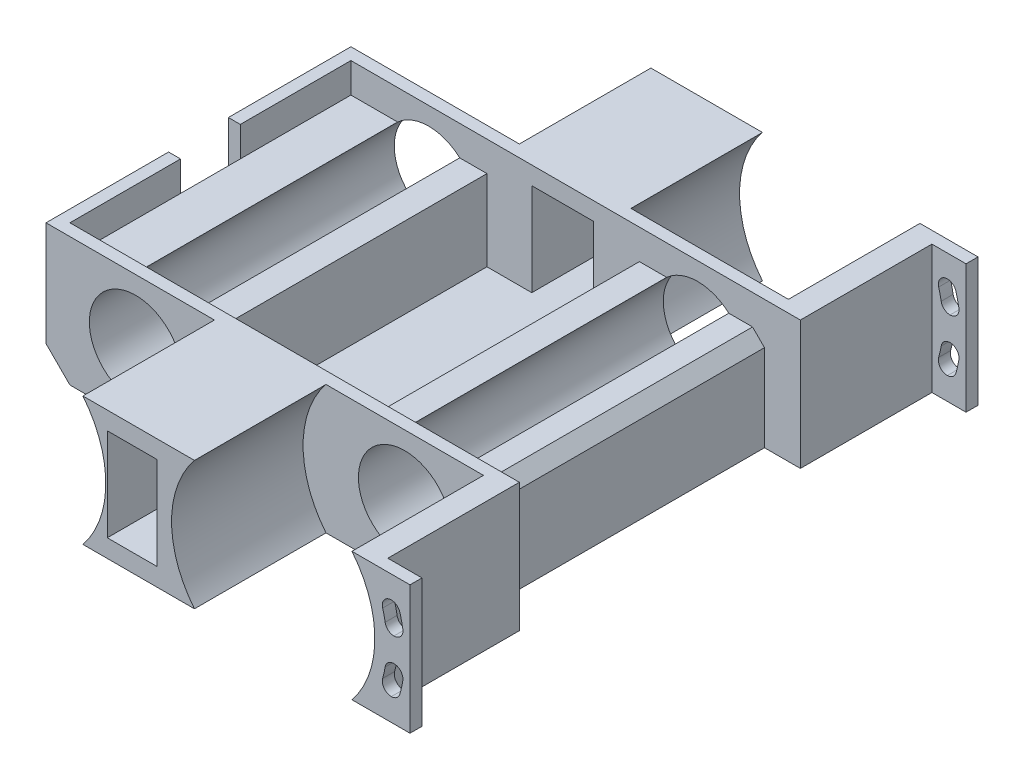
SolidWorks part; units mm, degrees
ref_plane "Front Plane" through (0, 0, 0) normal (0, 0, 1) x (1, 0, 0)
ref_plane "Top Plane" through (0, 0, 0) normal (0, 1, 0) x (1, 0, 0)
ref_plane "Right Plane" through (0, 0, 0) normal (1, 0, 0) x (0, 0, -1)
sketch "Sketch1" plane through (0, 0, 0) normal (0, 1, 0) x (1, 0, 0)
  line L1 (-44.2281, 29.9937) -> (50.7719, 29.9937)
  line L2 (-44.2281, 29.9937) -> (-44.2281, -65.0063)
  line L3 (-44.2281, -65.0063) -> (50.7719, -65.0063)
  line L4 (50.7719, 29.9937) -> (50.7719, -65.0063)
  dimension "D1" = 95
  dimension "D2" = 95
extrude "Boss-Extrude1" add sketch "Sketch1" along normal blind 25
sketch "Sketch2" plane through (0, 0, 65.0063) normal (0, 0, 1) x (1, 0, 0)
  line L1 (-44.2281, 0) -> (50.7719, 0) construction
  line L2 (-44.2281, 25) -> (-44.2281, 0) construction
  circle A0 centre (-29.2281, 10.75) radius 7.75
  circle A1 centre (15.7719, 10.75) radius 7.75
  point P6 (-44.2281, 12.5)
  dimension "D1" = 45
  dimension "D2" = 10.75
  dimension "D3" = 15
extrude "Cut-Extrude2" cut sketch "Sketch2" against normal blind 100
sketch "Sketch3" plane through (0, 0, 65.0063) normal (0, 0, 1) x (1, 0, 0)
  line L0 (-44.2281, 0) -> (50.7719, 0) construction
  circle A0 centre (-29.2281, 10.75) radius 17
  circle A1 centre (15.7719, 10.75) radius 17
  point P7 (-28.0903, 8.1892)
  dimension "D1" = 45
  dimension "D2" = 10.75
extrude "Cut-Extrude3" cut sketch "Sketch3" against normal blind 22
sketch "Sketch4" plane through (0, 0, -29.9937) normal (0, 0, -1) x (-1, 0, 0)
  circle A0 centre (-15.7719, 10.75) radius 17
  circle A1 centre (29.2281, 10.75) radius 17
extrude "Cut-Extrude4" cut sketch "Sketch4" against normal blind 22
sketch "Sketch5" plane through (0, 0, 65.0063) normal (0, 0, 1) x (1, 0, 0)
  line L1 (-44.2281, 25) -> (-37.9811, 25)
  line L2 (-44.2281, 25) -> (-44.2281, 0)
  line L3 (-44.2281, 0) -> (-37.9811, 0)
  line L4 (-37.9811, 25) -> (-37.9811, 0)
extrude "Cut-Extrude5" cut sketch "Sketch5" against normal blind 22
sketch "Sketch6" plane through (0, 0, -29.9937) normal (0, 0, -1) x (-1, 0, 0)
  line L1 (44.2281, 25) -> (37.0493, 25)
  line L2 (44.2281, 25) -> (44.2281, 0)
  line L3 (44.2281, 0) -> (37.0493, 0)
  line L4 (37.0493, 25) -> (37.0493, 0)
extrude "Cut-Extrude6" cut sketch "Sketch6" against normal blind 22
sketch "Sketch8" plane through (0, 0, -29.9937) normal (0, 0, -1) x (-1, 0, 0)
  line L1 (-50.7719, 25) -> (48.732, 25)
  line L2 (-50.7719, 25) -> (-50.7719, 21.5)
  line L3 (-50.7719, 21.5) -> (48.732, 21.5)
  line L4 (48.732, 25) -> (48.732, 21.5)
  dimension "D1" = 3.5
extrude "Cut-Extrude7" cut sketch "Sketch8" against normal blind 100
sketch "Sketch9" plane through (0, 0, 65.0063) normal (0, 0, 1) x (1, 0, 0)
  line L0 (-16.0585, 0) -> (2.6024, 0) construction
  line L1 (-11.9781, 18.5) -> (-3.6781, 18.5)
  line L2 (-11.9781, 18.5) -> (-11.9781, 3)
  line L3 (-11.9781, 3) -> (-3.6781, 3)
  line L4 (-3.6781, 18.5) -> (-3.6781, 3)
  arc A0 (-16.0585, 0) -> (-16.0585, 21.5) centre (-29.2281, 10.75) ccw construction
  circle A1 centre (15.7719, 10.75) radius 7.75 construction
  dimension "D1" = 8.3
  dimension "D2" = 15.5
  dimension "D3" = 3
  dimension "D4" = 17.25
  dimension "D5" = 19.45
extrude "Cut-Extrude11" cut sketch "Sketch9" against normal blind 100
sketch "Sketch13" plane through (-3.6781, 0, 0) normal (-1, 0, 0) x (0, 0, 1)
  line L0 (-29.9937, 3) -> (65.0063, 3) construction
  line L1 (-25.9937, 3) -> (61.0063, 3)
  line L2 (-25.9937, 3) -> (-25.9937, 18.5)
  line L3 (-25.9937, 18.5) -> (61.0063, 18.5)
  line L4 (61.0063, 3) -> (61.0063, 18.5)
  line L5 (-29.9937, 18.5) -> (65.0063, 18.5) construction
  line L6 (-29.9937, 3) -> (-29.9937, 18.5) construction
  line L7 (65.0063, 3) -> (65.0063, 18.5) construction
  dimension "D1" = 4
  dimension "D2" = 4
extrude "Cut-Extrude12" cut sketch "Sketch13" against normal blind 2
sketch "Sketch14" plane through (0, 21.5, 0) normal (0, 1, 0) x (1, 0, 0)
  line L2 (6.0219, 5.9937) -> (6.0219, -41.0063)
  line L4 (-19.4781, 5.9937) -> (-19.4781, -41.0063)
  line L7 (6.0219, 5.9937) -> (-19.4781, 5.9937)
  line L9 (6.0219, -41.0063) -> (-19.4781, -41.0063)
  dimension "D2" = 2
extrude "Cut-Extrude14" cut sketch "Sketch14" against normal blind 18.5
sketch "Sketch16" plane through (0, 21.5, 0) normal (0, 1, 0) x (1, 0, 0)
  line L0 (-44.2281, -43.0063) -> (-44.2281, 7.9937) construction
  line L1 (-17.4781, 5.9937) -> (-42.2281, 5.9937)
  line L2 (-17.4781, 5.9937) -> (-17.4781, -41.0063)
  line L3 (-17.4781, -41.0063) -> (-42.2281, -41.0063)
  line L4 (-42.2281, 5.9937) -> (-42.2281, -41.0063)
  line L5 (-44.2281, -43.0063) -> (-16.0585, -43.0063) construction
  line L6 (-16.0585, 7.9937) -> (-44.2281, 7.9937) construction
  dimension "D1" = 2
  dimension "D2" = 2
  dimension "D3" = 2
  dimension "D4" = 2
extrude "Cut-Extrude15" cut sketch "Sketch16" against normal blind 5
sketch "Sketch17" plane through (0, 21.5, 0) normal (0, 1, 0) x (1, 0, 0)
  line L0 (2.6024, -43.0063) -> (28.9415, -43.0063) construction
  line L1 (6.0219, 5.9937) -> (26.9415, 5.9937)
  line L2 (6.0219, 5.9937) -> (6.0219, -41.0063)
  line L3 (6.0219, -41.0063) -> (26.9415, -41.0063)
  line L4 (26.9415, 5.9937) -> (26.9415, -41.0063)
  dimension "D1" = 2
  dimension "D2" = 2
extrude "Cut-Extrude16" cut sketch "Sketch17" against normal blind 5
sketch "Sketch18" plane through (0, 0, 65.0063) normal (0, 0, 1) x (1, 0, 0)
  line L0 (34.6664, 12.75) -> (37.6809, 12.75)
  line L2 (34.6664, 8.75) -> (37.6809, 8.75)
  line L3 (33.4355, 17.75) -> (36.6286, 17.75)
  line L4 (33.4355, 3.75) -> (36.6286, 3.75)
  arc A0 (36.6286, 3.75) -> (37.6809, 8.75) centre (15.7719, 10.75) ccw
  arc A1 (33.4355, 3.75) -> (34.6664, 8.75) centre (15.7719, 10.75) ccw
  arc A2 (34.6664, 12.75) -> (33.4355, 17.75) centre (15.7719, 10.75) ccw
  arc A3 (37.6809, 12.75) -> (36.6286, 17.75) centre (15.7719, 10.75) ccw
  dimension "D1" = 44
  dimension "D2" = 38
  dimension "D4" = 5
  dimension "D6" = 5
extrude "Cut-Extrude17" cut sketch "Sketch18" against normal blind 100
fillet "Fillet6" radius 1.5 2 edges at (33.4355, 17.75, 17.5063) (36.6286, 17.75, 17.5063)
fillet "Fillet7" radius 1.5 2 edges at (37.6809, 12.75, 17.5063) (34.6664, 12.75, 17.5063)
fillet "Fillet8" radius 1.5 2 edges at (33.4355, 3.75, 17.5063) (36.6286, 3.75, 17.5063)
fillet "Fillet9" radius 1.5 2 edges at (37.6809, 8.75, 17.5063) (34.6664, 8.75, 17.5063)
sketch "Sketch19" plane through (0, 0, 65.0063) normal (0, 0, 1) x (1, 0, 0)
  line L1 (28.9415, 0) -> (50.7719, 0) construction
  line L2 (38.6507, 0) -> (50.7719, 0)
  line L3 (38.6507, 0) -> (38.6507, 21.5)
  line L4 (38.6507, 21.5) -> (50.7719, 21.5)
  line L5 (50.7719, 0) -> (50.7719, 21.5)
extrude "Cut-Extrude20" cut sketch "Sketch19" against normal blind 100
sketch "Sketch20" plane through (0, 21.5, 0) normal (0, 1, 0) x (1, 0, 0)
  line L0 (38.6507, -65.0063) -> (38.6507, 29.9937) construction
  line L1 (38.6507, -63.0063) -> (32.9415, -63.0063)
  line L2 (38.6507, -63.0063) -> (38.6507, 27.9937)
  line L3 (38.6507, 27.9937) -> (32.9415, 27.9937)
  line L4 (32.9415, -63.0063) -> (32.9415, 27.9937)
  line L5 (38.6507, 29.9937) -> (28.9415, 29.9937) construction
  line L6 (38.6507, -65.0063) -> (28.9415, -65.0063) construction
  line L7 (28.9415, -65.0063) -> (28.9415, -43.0063) construction
  dimension "D1" = 2
  dimension "D2" = 2
  dimension "D3" = 4
extrude "Cut-Extrude23" cut sketch "Sketch20" against normal blind 100
sketch "Sketch21" plane through (0, 21.5, 0) normal (0, 1, 0) x (1, 0, 0)
  line L0 (32.9415, 27.9937) -> (32.9415, -63.0063) construction
  line L1 (26.9415, -41.0063) -> (32.9415, -41.0063)
  line L2 (26.9415, -41.0063) -> (26.9415, 5.9937)
  line L3 (26.9415, 5.9937) -> (32.9415, 5.9937)
  line L4 (32.9415, -41.0063) -> (32.9415, 5.9937)
  line L6 (28.9415, 7.9937) -> (2.6024, 7.9937) construction
  dimension "D1" = 2
extrude "Cut-Extrude26" cut sketch "Sketch21" against normal blind 40
chamfer "Chamfer1" distance 2 angle 45 1 edges at (26.9415, 16.5, 17.5063)
sketch "Sketch22" plane through (0, 0, 0) normal (0, -1, 0) x (-1, 0, 0)
  line L0 (44.2281, 7.9937) -> (44.2281, -43.0063) construction
  line L1 (42.2281, -12.5063) -> (27.2281, -12.5063)
  line L2 (42.2281, -12.5063) -> (42.2281, -22.5063)
  line L3 (42.2281, -22.5063) -> (27.2281, -22.5063)
  line L4 (27.2281, -12.5063) -> (27.2281, -22.5063)
  line L5 (16.0585, 7.9937) -> (44.2281, 7.9937) construction
  line L6 (44.2281, -43.0063) -> (16.0585, -43.0063) construction
  dimension "D1" = 10
  dimension "D2" = 15
  dimension "D3" = 2
  dimension "D4" = 20.5
  dimension "D5" = 20.5
extrude "Cut-Extrude27" cut sketch "Sketch22" against normal blind 4
sketch "Sketch23" plane through (0, 0, 0) normal (0, -1, 0) x (-1, 0, 0)
  line L0 (44.2281, 7.9937) -> (44.2281, -43.0063) construction
  line L1 (42.2281, -12.5063) -> (44.2281, -12.5063)
  line L2 (42.2281, -12.5063) -> (42.2281, -22.5063)
  line L3 (42.2281, -22.5063) -> (44.2281, -22.5063)
  line L4 (44.2281, -12.5063) -> (44.2281, -22.5063)
  dimension "D1" = 10
extrude "Cut-Extrude28" cut sketch "Sketch23" against normal blind 54
chamfer "Chamfer2" distance 2 angle 45 1 edges at (-42.2281, 4, 17.5063)
chamfer "Chamfer3" distance 4 angle 45 1 edges at (-44.2281, 0, 2.2563)
chamfer "Chamfer4" distance 4 angle 45 1 edges at (-44.2281, 0, 32.7563)
